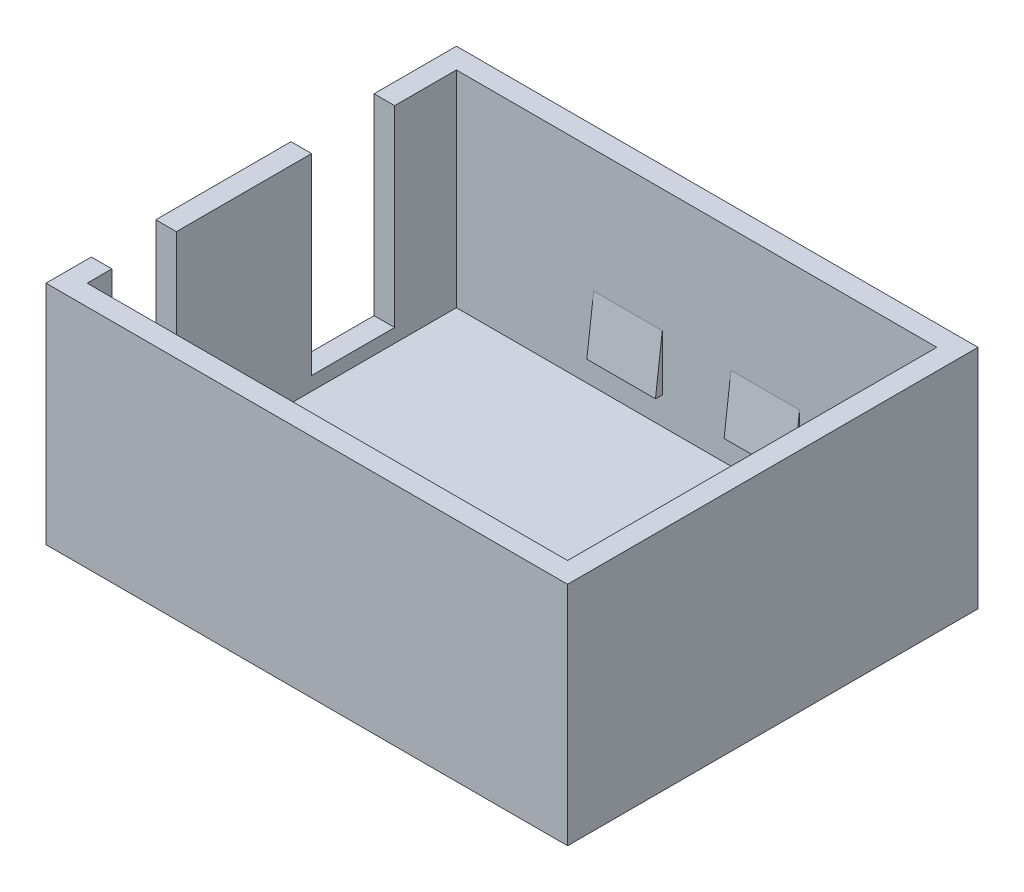
SolidWorks part; units mm, degrees
ref_plane "Alzado" through (0, 0, 0) normal (0, 0, 1) x (1, 0, 0)
ref_plane "Planta" through (0, 0, 0) normal (0, 1, 0) x (1, 0, 0)
ref_plane "Vista lateral" through (0, 0, 0) normal (1, 0, 0) x (0, 0, -1)
sketch "Croquis1" plane through (0, 0, 0) normal (0, 1, 0) x (1, 0, 0)
  line L0 (-38, -29.9) -> (-38, 29.9)
  line L1 (-35, -26.9) -> (35, -26.9)
  line L2 (-35, -26.9) -> (-35, 26.9)
  line L3 (-35, 26.9) -> (35, 26.9)
  line L4 (35, -26.9) -> (35, 26.9)
  line L5 (-35, -26.9) -> (35, 26.9) construction
  line L6 (-35, 26.9) -> (35, -26.9) construction
  line L7 (-38, 29.9) -> (38, 29.9)
  line L8 (38, -29.9) -> (38, 29.9)
  line L9 (-38, -29.9) -> (38, -29.9)
  point P0 (0, 0)
  dimension "D1" = 53.8
  dimension "D2" = 70
  dimension "D3" = 3
extrude "Saliente-Extruir1" add sketch "Croquis1" along normal mid plane 30
sketch "Croquis3" plane through (0, -15, 0) normal (0, -1, 0) x (1, 0, 0)
  line L12 (38, 29.9) -> (-38, 29.9)
  line L13 (-38, 29.9) -> (-38, -29.9)
  line L14 (-38, -29.9) -> (38, -29.9)
  line L15 (38, -29.9) -> (38, 29.9)
  line L16 (38, 29.9) -> (-38, 29.9)
  line L17 (-38, 29.9) -> (-38, -29.9)
  line L18 (-38, -29.9) -> (38, -29.9)
  line L19 (38, -29.9) -> (38, 29.9)
  dimension "D2" = 0
extrude "Saliente-Extruir2" add sketch "Croquis3" along normal blind 3
sketch "Croquis4" plane through (0, 15, 0) normal (0, 1, 0) x (1, 0, 0)
  line L3 (-38, 29.9) -> (-38, -29.9) construction
  line L4 (-35, 26.9) -> (-35, -26.9) construction
  line L5 (-41, 17.9) -> (-35, 17.9)
  line L6 (-41, 17.9) -> (-41, 5.8)
  line L7 (-41, 5.8) -> (-35, 5.8)
  line L8 (-35, 17.9) -> (-35, 5.8)
  line L9 (-41, 17.9) -> (-35, 5.8) construction
  line L10 (-41, 5.8) -> (-35, 17.9) construction
  line L11 (-35, 26.9) -> (-35, -26.9) construction
  line L12 (-41, -13.9) -> (-35, -13.9)
  line L13 (-41, -13.9) -> (-41, -23.3)
  line L14 (-41, -23.3) -> (-35, -23.3)
  line L15 (-35, -13.9) -> (-35, -23.3)
  line L16 (-41, -13.9) -> (-35, -23.3) construction
  line L17 (-41, -23.3) -> (-35, -13.9) construction
  line L18 (-35, -26.9) -> (35, -26.9) construction
  line L19 (35, 26.9) -> (-35, 26.9) construction
  point P1 (-38, -18.6)
  point P2 (-38, 11.85)
  dimension "D1" = 3.6
  dimension "D2" = 9.4
  dimension "D3" = 9
  dimension "D4" = 12.1
  dimension "D5" = 19.7
extrude "Cortar-Extruir1" cut sketch "Croquis4" against normal blind 28
sketch "Croquis5" plane through (0, 0, 0) normal (1, 0, 0) x (0, 0, -1)
  line L0 (-26.9, -2.3975) -> (-25.9051, -10.5)
  line L1 (-26.9, 15) -> (-26.9, -15) construction
  line L2 (-25.9051, -10.5) -> (-26.9, -10.5)
  line L3 (-26.9, -2.3975) -> (-26.9, -10.5)
  line L4 (26.9, -15) -> (-26.9, -15) construction
  dimension "D1" = 0.9949
  dimension "D2" = 7
  dimension "D3" = 4.5
extrude "Saliente-Extruir3" add sketch "Croquis5" along normal mid plane 10
ref_plane "Plano1" through (10, 0, 0) normal (1, 0, 0) x (0, 0, -1)
sketch "Croquis6" plane through (10, 0, -10) normal (-1, 0, 0) x (0, 0, 1)
  line L0 (-16.9, -2.8975) -> (-15.9051, -11)
  line L2 (-15.9051, -11) -> (-16.9, -11)
  line L3 (-16.9, -2.8975) -> (-16.9, -11)
  line L5 (-16.9, 15) -> (-16.9, -15) construction
  line L6 (-16.9, -15) -> (36.9, -15) construction
  point P2 (-16.9, -9.083)
  dimension "D1" = 0.9949
  dimension "D2" = 7
  dimension "D3" = 4
extrude "Saliente-Extruir4" add sketch "Croquis6" along normal mid plane 10
pattern_linear "MatrizL1" count 2 spacing 20 along (-1, 0, 0) of "Saliente-Extruir4"
pattern_linear "MatrizL2" count 2 spacing 20 along (1, 0, 0) count 2 spacing 20 along (-1, 0, 0) of "Saliente-Extruir3" pattern seed only yes
